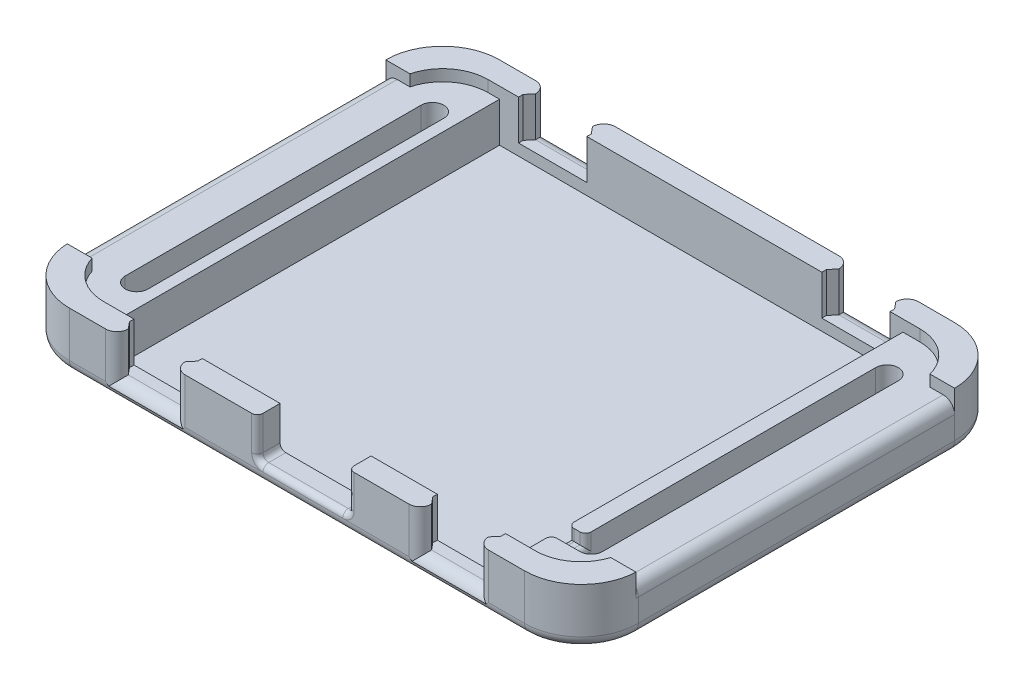
SolidWorks part; units mm, degrees
material "ABS"
ref_plane "Front Plane" through (0, 0, 0) normal (0, 0, 1) x (1, 0, 0)
ref_plane "Top Plane" through (0, 0, 0) normal (0, 1, 0) x (1, 0, 0)
ref_plane "Right Plane" through (0, 0, 0) normal (1, 0, 0) x (0, 0, -1)
sketch "Sketch1" plane through (0, 0, 0) normal (0, 1, 0) x (1, 0, 0)
  line L1 (-25, -18.9) -> (25, -18.9)
  line L2 (-25, -18.9) -> (-25, 18.9)
  line L3 (-25, 18.9) -> (25, 18.9)
  line L4 (25, -18.9) -> (25, 18.9)
  line L5 (-25, -18.9) -> (25, 18.9) construction
  line L6 (-25, 18.9) -> (25, -18.9) construction
  point P0 (0, 0)
extrude "Case" add sketch "Sketch1" along normal blind 5
sketch "Sketch7" plane through (0, 5, 0) normal (0, 1, 0) x (1, 0, 0)
  line L0 (-22.8158, -14.1) -> (-22.873, 13.9)
  line L1 (-19, 16.9) -> (18.96, 16.9)
  line L2 (22.833, 13.9) -> (22.7758, -14.1)
  line L3 (18.96, -16.9) -> (-19, -16.9)
  arc A0 (-22.873, 13.9) -> (-19, 16.9) centre (-19, 12.9) cw
  arc A1 (22.833, 13.9) -> (18.96, 16.9) centre (18.96, 12.9) ccw
  arc A2 (22.7758, -14.1) -> (18.96, -16.9) centre (18.96, -12.9) cw
  arc A3 (-22.8158, -14.1) -> (-19, -16.9) centre (-19, -12.9) ccw
  point P18 (0, 0)
  point P21 (0, 0)
  point P22 (0, 0)
  point P23 (0, 0)
  point P24 (0, 0)
  point P25 (0, 0)
  point P26 (0, 0)
  point P27 (0, 0)
sketch "Sketch2" plane through (0, 5, 0) normal (0, 1, 0) x (1, 0, 0)
  line L1 (-18, -16.9) -> (17.46, -16.9)
  line L2 (-18, -16.9) -> (-18, 16.9)
  line L3 (-18, 16.9) -> (17.46, 16.9)
  line L4 (17.46, -16.9) -> (17.46, 16.9)
  point P0 (0, 0)
extrude "Cut-Extrude1" cut sketch "Sketch2" against normal blind 4.5
sketch "Sketch3" plane through (0, 5, 0) normal (0, 1, 0) x (1, 0, 0)
  line L0 (-21, 13) -> (-21, -13)
  line L2 (-19, -13) -> (-19, 13)
  line L3 (20.96, -13) -> (20.96, 13)
  line L4 (18.96, 13) -> (18.96, -8.95)
  line L8 (18.96, -8.95) -> (18.96, -13)
  arc A0 (-21, -13) -> (-19, -13) centre (-20, -13) ccw
  arc A1 (-19, 13) -> (-21, 13) centre (-20, 13) ccw
  arc A2 (20.96, 13) -> (18.96, 13) centre (19.96, 13) ccw
  arc A3 (18.96, -13) -> (20.96, -13) centre (19.96, -13) ccw
  point P15 (0, 0)
  point P16 (0, 0)
  point P19 (0, 0)
  point P22 (0, 0)
  point P24 (0, 0)
  point P27 (0, 0)
  point P28 (0, 0)
  point P29 (0, 0)
  point P30 (0, 0)
  point P31 (0, 0)
  point P32 (0, 0)
extrude "Cut-Extrude2" cut sketch "Sketch3" along direction (0, -1, 0) on the side against the normal through all
sketch "Sketch4" plane through (0, 5, 0) normal (0, 1, 0) x (1, 0, 0)
  line L0 (-26.9259, 13.9) -> (27.9637, 13.9) construction
  line L2 (27.9637, -14.1) -> (-26.9259, -14.1) construction
  line L3 (-27.2213, -14.1) -> (28.0612, -14.1)
  line L4 (-27.2213, -14.1) -> (-27.2213, 13.9)
  line L5 (-27.2213, 13.9) -> (28.0612, 13.9)
  line L6 (28.0612, -14.1) -> (28.0612, 13.9)
extrude "Cut-Extrude3" cut sketch "Sketch4" against normal blind 1
sketch "Sketch5" plane through (0, 5, 0) normal (0, 1, 0) x (1, 0, 0)
  line L0 (-25, -18.9) -> (25, -18.9) construction
  line L1 (-3.49, -16.9) -> (4.51, -16.9)
  line L2 (-3.49, -16.9) -> (-3.49, -18.9)
  line L3 (-3.49, -18.9) -> (4.51, -18.9)
  line L4 (4.51, -16.9) -> (4.51, -18.9)
  line L7 (25, -18.9) -> (15.83, -18.9) construction
  line L9 (15.83, -18.9) -> (10.83, -18.9)
  line L11 (15.83, -16.9) -> (10.83, -16.9)
  line L13 (0, 0) -> (28.8794, 0) construction
  line L14 (0, 0) -> (0, 28.8305) construction
  line L29 (10.83, 16.9) -> (10.33, 16.9)
  line L34 (10.33, 16.9) -> (10.33, 17.3)
  line L35 (10.83, 18.9) -> (10.83, 17.9)
  line L36 (10.33, 17.3) -> (10.83, 17.9)
  line L37 (16.33, 17.3) -> (15.83, 17.9)
  line L38 (15.83, 18.9) -> (15.83, 17.9)
  line L39 (16.33, 16.9) -> (16.33, 17.3)
  line L40 (15.83, 16.9) -> (16.33, 16.9)
  line L41 (15.83, 16.9) -> (10.83, 16.9)
  line L42 (15.83, 18.9) -> (10.83, 18.9)
  line L43 (-10.83, -16.9) -> (-10.33, -16.9)
  line L44 (-10.33, -16.9) -> (-10.33, -17.3)
  line L45 (-10.83, -18.9) -> (-10.83, -17.9)
  line L46 (-10.33, -17.3) -> (-10.83, -17.9)
  line L47 (-16.33, -17.3) -> (-15.83, -17.9)
  line L48 (-15.83, -18.9) -> (-15.83, -17.9)
  line L49 (-16.33, -16.9) -> (-16.33, -17.3)
  line L50 (15.83, -16.9) -> (16.33, -16.9)
  line L51 (16.33, -16.9) -> (16.33, -17.3)
  line L52 (15.83, -18.9) -> (15.83, -17.9)
  line L53 (16.33, -17.3) -> (15.83, -17.9)
  line L54 (10.33, -17.3) -> (10.83, -17.9)
  line L55 (10.83, -18.9) -> (10.83, -17.9)
  line L56 (10.33, -16.9) -> (10.33, -17.3)
  line L57 (10.83, -16.9) -> (10.33, -16.9)
  line L58 (-15.83, -16.9) -> (-16.33, -16.9)
  line L59 (-15.83, 18.9) -> (-10.83, 18.9)
  line L60 (-15.83, 16.9) -> (-10.83, 16.9)
  line L61 (-15.83, 16.9) -> (-16.33, 16.9)
  line L62 (-16.33, 16.9) -> (-16.33, 17.3)
  line L63 (-15.83, 18.9) -> (-15.83, 17.9)
  line L64 (-16.33, 17.3) -> (-15.83, 17.9)
  line L65 (-10.33, 17.3) -> (-10.83, 17.9)
  line L66 (-10.83, 18.9) -> (-10.83, 17.9)
  line L67 (-10.33, 16.9) -> (-10.33, 17.3)
  line L68 (-10.83, 16.9) -> (-10.33, 16.9)
  line L69 (-15.83, -16.9) -> (-10.83, -16.9)
  line L70 (-15.83, -18.9) -> (-10.83, -18.9)
  point P0 (0, -18.9)
  point P14 (0, 0)
  point P15 (0, 0)
  dimension "D1" = 5
  dimension "D3" = 8
extrude "Cut-Extrude4" cut sketch "Sketch5" against normal blind 3.5
fillet "Fillet1" radius 5 4 edges at (-25, 2.5, 18.9) (-25, 2.5, -18.9) (25, 2.5, -18.9) (25, 2.5, 18.9)
fillet "Fillet2" radius 1 32 edges at (23.5355, 0, 17.4355) (25, 0, 0) (23.5355, 0, -17.4355) (0, 0, -18.9) (-23.5355, 0, -17.4355) (-25, 0, 0) (-23.5355, 0, 17.4355) (0, 0, 18.9) (20.96, 0, 0) (19.96, 0, 14) (18.96, 0, 0) (19.96, 0, -14) (-19, 0, 0) (-20, 0, 14) (-21, 0, 0) (-20, 0, -14) (13.33, 1.5, 18.9) (-15.83, 3.25, 18.9) (-13.33, 1.5, 18.9) (-10.83, 3.25, 18.9) (10.83, 3.25, 18.9) (15.83, 3.25, 18.9) (15.83, 3.25, -18.9) (13.33, 1.5, -18.9) (10.83, 3.25, -18.9) (-10.83, 3.25, -18.9) (-13.33, 1.5, -18.9) (-15.83, 3.25, -18.9) (-24.999, 4, 14) (24.999, 4, 14) (-25, 4, 0) (25, 4, 0)
sketch "Sketch6" plane through (0, 4, 0) normal (0, 1, 0) x (1, 0, 0)
  line L0 (19.96, -14) -> (17.46, -14)
  line L2 (17.46, -14) -> (17.46, -12.5)
  line L3 (17.46, -12.5) -> (18.96, -12.5)
  line L5 (18.96, -12.5) -> (19.96, -14)
  point P2 (0, 0)
  point P3 (0, 0)
  point P4 (0, 0)
  point P7 (0, 0)
extrude "Cut-Extrude5" cut sketch "Sketch6" against normal blind 1
fillet "Fillet3" radius 0.5 6 edges at (18.96, 3, 12.75) (18.96, 3.5, 12.5) (17.46, 3.5, 12.5) (17.46, 3.5, 14) (17.46, 3, 13.25) (19.2529, 3, 13.7071)
fillet "Fillet4" radius 0.5 5 edges at (-3.49, 3.25, 18.9) (0.51, 1.5, 18.9) (4.51, 3.25, 18.9) (4.51, 1.5, 17.9) (-3.49, 1.5, 17.9)
extrude "Cut-Extrude6" cut sketch "Sketch7" against normal blind 1
